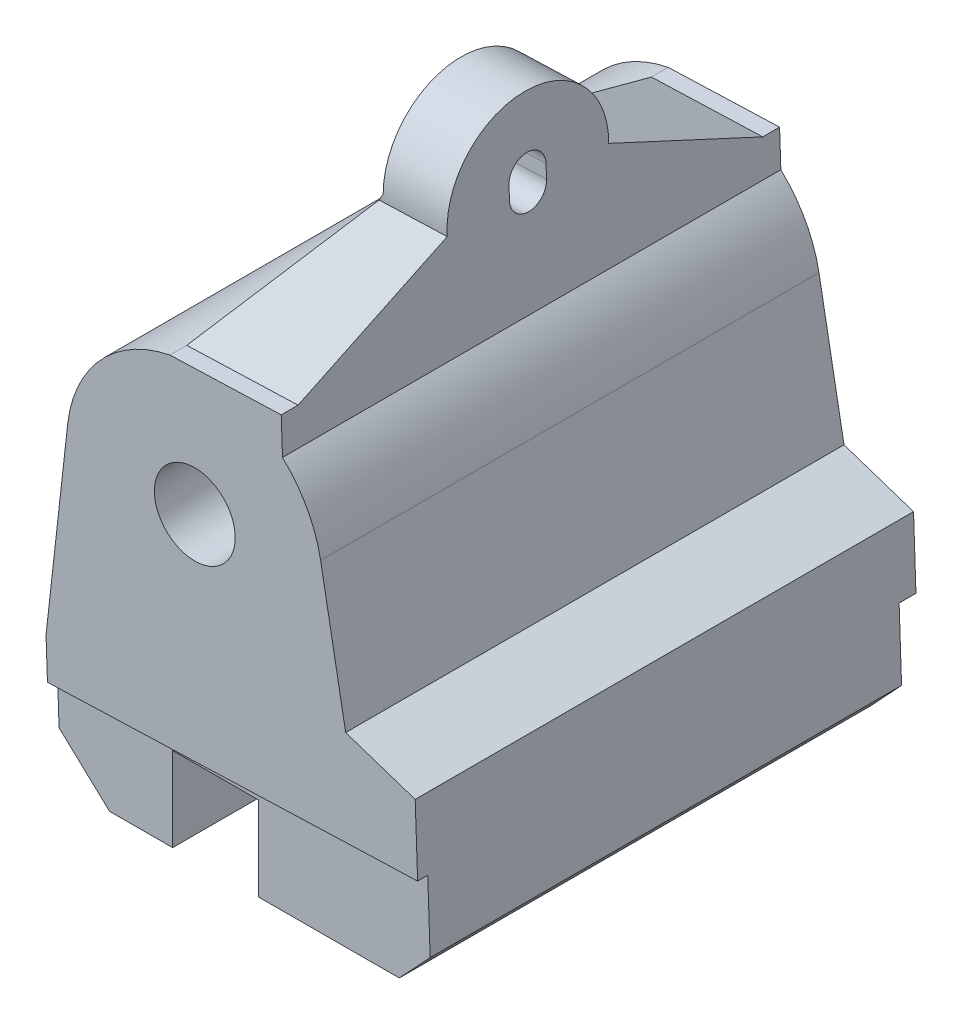
SolidWorks part; units mm, degrees
ref_plane "前视基准面" through (0, 0, 0) normal (0, 0, 1) x (1, 0, 0)
ref_plane "上视基准面" through (0, 0, 0) normal (0, 1, 0) x (1, 0, 0)
ref_plane "右视基准面" through (0, 0, 0) normal (1, 0, 0) x (0, 0, -1)
sketch "草图1" plane through (0, 0, 0) normal (0, 0, 1) x (1, 0, 0)
  line L0 (-92, -103) -> (-75.1879, 11.0805)
  line L1 (-92, -103) -> (-92, -153)
  line L2 (-92, -153) -> (-63, -182)
  line L3 (-63, -182) -> (-25.5545, -183.2345)
  line L4 (-25.5545, -183.2345) -> (-23.9079, -133.2846)
  line L5 (-23.9079, -133.2846) -> (27.0645, -134.965)
  line L6 (27.0645, -134.965) -> (25.4178, -184.9149)
  line L7 (25.4178, -184.9149) -> (109, -187.6703)
  line L8 (109, -187.6703) -> (128, -168.6703)
  line L9 (128, -168.6703) -> (128, -85.6703)
  line L10 (128, -85.6703) -> (32, -50) construction
  line L11 (75.1879, 11.0805) -> (92, -103) construction
  line L12 (0, 0) -> (0, -182) construction
  line L13 (-63, -182) -> (167.1773, -182) construction
  line L14 (-25.5545, -183.2345) -> (25.4178, -184.9149) construction
  line L15 (0, -182) -> (6, 0) construction
  line L16 (-63, -182) -> (-63, 0) construction
  line L17 (-63, -182) -> (-57, 0) construction
  line L18 (0, 0) -> (-116.977, 0) construction
  line L19 (0, 0) -> (32, 0) construction
  line L20 (0, -50) -> (32, -50) construction
  line L21 (0, -50) -> (-116.977, -50) construction
  line L22 (75.1879, 11.0805) -> (87.2127, -70.5152)
  line L23 (87.2127, -70.5152) -> (128, -85.6703)
  circle A0 centre (0, 0) radius 24 construction
  arc A1 (-58.5956, -48.4) -> (-57.2364, -50) centre (0, 0) ccw
  arc A2 (0, -76) -> (3.4972, -75.9195) centre (0, 0) ccw
  arc A3 (75.1879, 11.0805) -> (-76, 0) centre (0, 0) ccw
  point P16 (6, 0)
  dimension "D1" = 48
  dimension "D2" = 152
  dimension "D3" = 182
  dimension "D4" = 45
  dimension "D5" = 29
  dimension "D6" = 79
  dimension "D7" = 92
  dimension "D8" = 220
  dimension "D9" = 45
  dimension "D10" = 134
  dimension "D11" = 6
  dimension "D12" = 6
  dimension "D13" = 25.5
  dimension "D14" = 51
  dimension "D15" = 19
  dimension "D16" = 102
  dimension "D18" = 32
  dimension "D17" = 50
extrude "凸台-拉伸1" add sketch "草图1" along normal blind 296 contours L22 A3 L0 L1 L2 L3 L4 L5 L6 L7 L8 L9 L23 region at (10.9362, -66.0561, 0)
sketch "草图2" plane through (0, 0, 296) normal (0, 0, 1) x (1, 0, 0)
  circle A0 centre (0, 0) radius 24
  dimension "D1" = 48
extrude "切除-拉伸1" cut sketch "草图2" against normal up to next
sketch "草图3" plane through (0, 0, 296) normal (0, 0, 1) x (1, 0, 0)
  line L0 (54, 53.479) -> (54, 166)
  line L1 (54, 166) -> (16, 166)
  line L2 (16, 166) -> (16, 120)
  line L3 (16, 120) -> (-25, 54.5436) construction
  line L4 (16, 120) -> (-12.1751, 75.0184)
  arc A0 (75.1879, 11.0805) -> (-75.1879, 11.0805) centre (0, 0) ccw construction
  arc A1 (54, 53.479) -> (-12.1751, 75.0184) centre (0, 0) ccw
  circle A2 centre (0, 0) radius 60 construction
  dimension "D5" = 120
  dimension "D1" = 348
  dimension "D2" = 54
  dimension "D3" = 38
  dimension "D4" = 120
  dimension "D6" = 41
extrude "凸台-拉伸2" add sketch "草图3" against normal up to surface (296 mm away) up to face at (24, 0, 0)
sketch "草图4" plane through (16, 0, 0) normal (-1, 0, 0) x (0, 0, 1)
  line L0 (148, 166) -> (148, -244.5055) construction
  line L1 (0, 166) -> (296, 166) construction
  line L3 (296, 24) -> (0, 24) construction
  line L4 (296, 24) -> (0, 24) construction
  line L5 (0, -24) -> (296, -24) construction
  line L6 (0, -24) -> (296, -24) construction
  line L7 (247.7162, 24) -> (247.7162, -24) construction
  line L8 (247.7162, 0) -> (364.965, 0) construction
  line L9 (148, 124) -> (148, 116) construction
  line L10 (159, 124) -> (159, 116)
  line L11 (137, 124) -> (137, 116)
  line L12 (0, 120) -> (296, 120) construction
  arc A0 (159, 124) -> (137, 124) centre (148, 124) ccw
  arc A1 (137, 116) -> (159, 116) centre (148, 116) ccw
  point P15 (148, 120)
  dimension "D1" = 11
  dimension "D2" = 30
extrude "切除-拉伸2" cut sketch "草图4" against normal up to next and the other way up to next
sketch "草图5" plane through (16, 0, 0) normal (-1, 0, 0) x (0, 0, 1)
  line L0 (137, 120) -> (159, 120) construction
  circle A0 centre (148, 120) radius 38
  dimension "D1" = 76
extrude "切除-拉伸4" cut sketch "草图5" against normal blind 16 and the other way up to next
sketch "草图6" plane through (16, 0, 0) normal (-1, 0, 0) x (0, 0, 1)
  line L0 (296, 75.0184) -> (286, 75.0184)
  line L1 (0, 75.0184) -> (296, 75.0184) construction
  line L2 (286, 75.0184) -> (195.9583, 116)
  line L3 (100.0417, 116) -> (10, 75.0184)
  line L4 (10, 75.0184) -> (0, 75.0184)
  line L6 (0, -24) -> (296, -24) construction
  line L7 (0, -24) -> (296, -24) construction
  line L8 (296, 24) -> (0, 24) construction
  line L9 (296, 24) -> (0, 24) construction
  line L10 (148, 24) -> (148, -24) construction
  line L11 (148, 0) -> (407.4993, 0) construction
  line L12 (0, 166) -> (296, 166) construction
  line L14 (0, 75.0184) -> (0, 166)
  line L15 (0, 166) -> (148, 166)
  line L16 (148, 166) -> (296, 166)
  line L17 (296, 166) -> (296, 75.0184)
  arc A1 (195.9583, 116) -> (100.0417, 116) centre (148, 118) ccw
  line M11 (0, 120) -> (110, 120)
  line M13 (186, 120) -> (296, 120)
  line M14 (296, 120) -> (296, 166)
  line M15 (296, 166) -> (0, 166)
  line M16 (0, 166) -> (0, 120)
  dimension "D4" = 96
  dimension "D1" = 10
  dimension "D2" = 10
  dimension "D3" = 116
extrude "切除-拉伸10" cut sketch "草图6" against normal up to next contours A1 M13 M14 M15 region at (16, 144.1918, 240.1069)
extrude "切除-拉伸11" cut sketch "草图6<5>" against normal up to next contours A1 M15 M16 M11 region at (16, 144.1918, 55.8931)
sketch "草图6<5>" plane through (16, 0, 0) normal (-1, 0, 0) x (0, 0, 1) same geometry as "草图6"
extrude "切除-拉伸12" cut sketch "草图6<6>" against normal up to next and the other way up to next contours A1 L14 L4 L3 M11 | A1 L2 L0 L17 M13 region at (16, 103.645, 259.8851) region at (16, 103.645, 36.1149)
sketch "草图6<6>" plane through (16, 0, 0) normal (-1, 0, 0) x (0, 0, 1) same geometry as "草图6"
sketch "草图10" plane through (0, 0, 296) normal (0, 0, 1) x (1, 0, 0)
  line L0 (-141.0758, -127) -> (212.4784, -127)
  dimension "D1" = 127
extrude "切除-拉伸-薄壁1" cut sketch "草图10" against normal blind 6 and the other way through all flip side to cut thin thin type one direction wall 70
sketch "草图11" plane through (0, 0, 0) normal (0, 0, -1) x (-1, 0, 0)
  line L0 (-166.219, -127) -> (149.1003, -127)
  dimension "D1" = 127
extrude "切除-拉伸-薄壁2" cut sketch "草图11" against normal blind 10 and the other way through all thin thin type one direction wall 70
sketch "草图12" plane through (-6.0619, -183.8771, 0) normal (-0.0329, -0.9995, 0) x (0.9995, -0.0329, 0)
  line L0 (31.4967, 10) -> (115.1244, 10) construction
  line L1 (31.4967, 290) -> (-19.5033, 290) construction
  line L2 (31.4967, 262.5) -> (87.8436, 79.6571)
  line L3 (31.4967, 290) -> (31.4967, 10) construction
  line L4 (31.4967, 85.9319) -> (38.1498, 64.3429)
  line L5 (31.4967, 290) -> (31.4967, 10) construction
  line L6 (5.9967, 290) -> (5.9967, 10) construction
  line L7 (-19.5033, 10) -> (31.4967, 10) construction
  line L9 (31.4967, 262.5) -> (31.4967, 85.9319)
  arc A0 (38.1498, 64.3429) -> (87.8436, 79.6571) centre (62.9967, 72) ccw
  point P6 (5.9967, 290)
  dimension "D3" = 52
  dimension "D1" = 62
  dimension "D2" = 57
  dimension "D4" = 190.5
extrude "切除-拉伸13" cut sketch "草图12" against normal up to surface (49.977 mm away) up to face at (1.5783, -134.1248, 150)
ref_plane "基准面1" through (-6.0619, -183.8771, 0) normal (-0.0329, -0.9995, 0) x (-0.9995, 0.0329, 0)
move or copy body "实体-移动/复制1" bodies to move or copy 117 copy no rotation origin (18, -10.8352, 0) rotation axis (0, 0, 1) rotation angle 2
